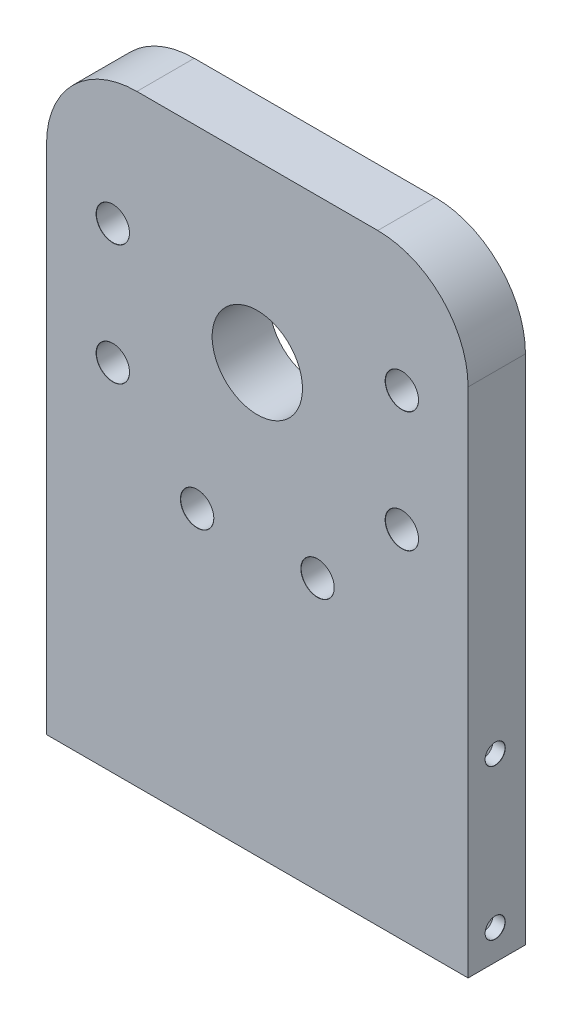
SolidWorks part; units mm, degrees
material "1060 Alloy"
ref_plane "Front Plane" through (0, 0, 0) normal (0, 0, 1) x (1, 0, 0)
ref_plane "Top Plane" through (0, 0, 0) normal (0, 1, 0) x (1, 0, 0)
ref_plane "Right Plane" through (0, 0, 0) normal (1, 0, 0) x (0, 0, -1)
sketch "Sketch1" plane through (0, 0, 0) normal (0, 0, 1) x (1, 0, 0)
  line L1 (-35, -50) -> (35, -50)
  line L2 (-35, -50) -> (-35, 50)
  line L3 (-35, 50) -> (35, 50)
  line L4 (35, -50) -> (35, 50)
  line L5 (-35, -50) -> (35, 50) construction
  line L6 (-35, 50) -> (35, -50) construction
  point P0 (0, 0)
  dimension "D1" = 100
  dimension "D2" = 70
extrude "Boss-Extrude1" add sketch "Sketch1" along normal blind 9.525
sketch "Sketch2" plane through (0, -50, 0) normal (0, -1, 0) x (1, 0, 0)
  line L0 (-35, 4.7625) -> (35, 4.7625) construction
  line L1 (-35, 9.525) -> (-35, 0) construction
  line L2 (35, 9.525) -> (35, 0) construction
  line L3 (0, -55) -> (0, 55) construction
  point P6 (-20, 4.7625)
  point P9 (20, 4.7625)
  dimension "D1" = 15
hole_wizard "Tap Drill for M4x0.7 Tap1" positions "Sketch3" profile "Sketch4" hole size "M4x0.7" standard "ANSI Metric"
sketch "Sketch3" plane through (0, -50, 0) normal (0, -1, 0) x (-1, 0, 0)
  point P0 (20, -4.7625)
  point P3 (-20, -4.7625)
sketch "Sketch4" plane through (-20, -50, 4.7625) normal (1, 0, 0) x (0, 0, -1)
  line L0 (0, 0) -> (0, 2.9914)
  line L1 (0, 2.9914) -> (1.65, 2)
  line L2 (1.65, 2) -> (1.65, 0.025)
  line L3 (1.65, 0.025) -> (1.675, 0)
  line L5 (1.675, 0) -> (0, 0)
  line L6 (-1.65, 0.025) -> (-1.675, 0) construction
  line L10 (0, 2.9914) -> (-1.65, 2) construction
  line L11 (0, -6.35) -> (0, 107.95) construction
  dimension "Hole Dia." = 3.3
  dimension "Hole Depth" = 2
  dimension "Near C'Sink Dia." = 3.35
  dimension "Near C'Sink Angle" = 90
  dimension "Drill Angle" = 118
sketch "Sketch5" plane through (0, 0, 9.525) normal (0, 0, 1) x (1, 0, 0)
  line L0 (0, -5.2388) -> (0, 5.2388) construction
  line L2 (-35, -50) -> (35, -50) construction
  line L3 (35, 50) -> (-35, 50) construction
  point P0 (10, -5)
  point P1 (24, 9)
  point P2 (24, 29)
  point P3 (0, 21)
  point P8 (0, 50)
  point P11 (-24, 29)
  point P12 (-24, 9)
  point P13 (-10, -5)
  dimension "D1" = 26
  dimension "D2" = 10
  dimension "D3" = 20
  dimension "D4" = 8
  dimension "D5" = 24
  dimension "D6" = 45
sketch "Sketch6" plane through (0, 0, 9.525) normal (0, 0, 1) x (1, 0, 0)
  circle A0 centre (0, 21) radius 7.5
  dimension "D1" = 15
extrude "Cut-Extrude1" cut sketch "Sketch6" against normal through all
hole_wizard "M5 Clearance Hole1" positions "Sketch11" profile "Sketch12" hole size "M5" standard "ANSI Metric" end condition through all
sketch "Sketch11" plane through (0, 0, 9.525) normal (0, 0, 1) x (1, 0, 0)
  point P0 (-10, -5)
  point P3 (10, -5)
  point P6 (24, 9)
  point P9 (24, 29)
  point P12 (-24, 9)
  point P15 (-24, 29)
sketch "Sketch12" plane through (-10, -5, 9.525) normal (1, 0, 0) x (0, -1, 0)
  line L0 (0, 0) -> (0, 9.525)
  line L1 (0, 9.525) -> (2.75, 9.525)
  line L2 (2.75, 9.525) -> (2.75, 0.025)
  line L3 (2.75, 0.025) -> (2.775, 0)
  line L5 (2.775, 0) -> (0, 0)
  line L6 (-2.75, 0.025) -> (-2.775, 0) construction
  line L11 (0, -6.35) -> (0, 107.95) construction
  dimension "Thru Hole Dia." = 5.5
  dimension "Thru Hole Depth" = 9.525
  dimension "Near C'Sink Dia." = 5.55
  dimension "Near C'Sink Angle" = 90
sketch "Sketch13" plane through (35, 0, 0) normal (1, 0, 0) x (0, 0, -1)
  line L0 (-5.025, -35) -> (-5.025, 35) construction
  line L1 (-9.525, -50) -> (-9.525, 50) construction
  line L2 (-9.525, -50) -> (0, -50) construction
  point P2 (-5.025, -20)
  point P5 (-5.025, -45)
  dimension "D1" = 5
  dimension "D2" = 4.5
  dimension "D3" = 25
hole_wizard "Tap Drill for M4x0.7 Tap2" positions "Sketch14" profile "Sketch16" hole size "M4x0.7" standard "ANSI Metric"
sketch "Sketch14" plane through (35, 0, 0) normal (1, 0, 0) x (0, 0, -1)
  point P0 (-5.025, -45)
  point P3 (-5.025, -20)
sketch "Sketch16" plane through (35, -45, 5.025) normal (0, 1, 0) x (0, 0, -1)
  line L0 (0, 0) -> (0, 2.9914)
  line L1 (0, 2.9914) -> (1.65, 2)
  line L2 (1.65, 2) -> (1.65, 0.025)
  line L3 (1.65, 0.025) -> (1.675, 0)
  line L5 (1.675, 0) -> (0, 0)
  line L6 (-1.65, 0.025) -> (-1.675, 0) construction
  line L10 (0, 2.9914) -> (-1.65, 2) construction
  line L11 (0, -6.35) -> (0, 107.95) construction
  dimension "Hole Dia." = 3.3
  dimension "Hole Depth" = 2
  dimension "Near C'Sink Dia." = 3.35
  dimension "Near C'Sink Angle" = 90
  dimension "Drill Angle" = 118
mirror "Mirror1" about plane through (0, 0, 0) normal (1, 0, 0) of "Tap Drill for M4x0.7 Tap2"
fillet "Fillet1" radius 15 2 edges at (-35, 50, 4.7625) (35, 50, 4.7625)
